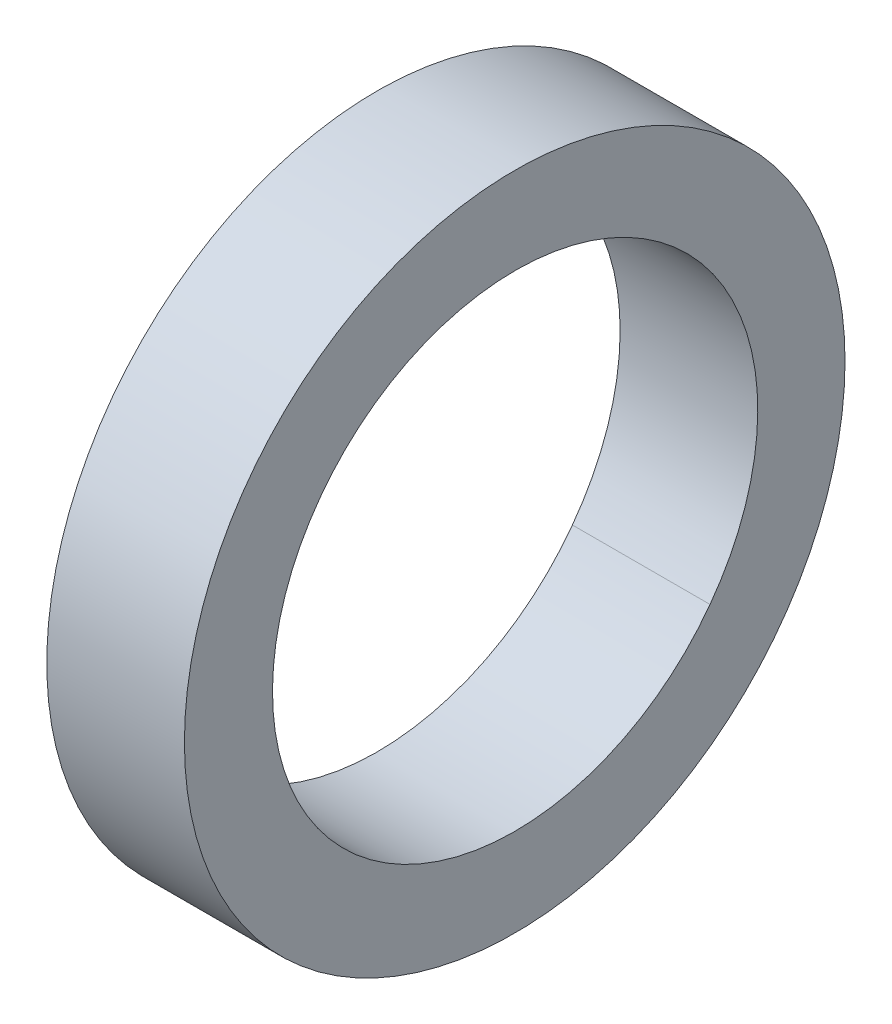
SolidWorks part; units mm, degrees
ref_plane "Front Plane" through (0, 0, 0) normal (0, 0, 1) x (1, 0, 0)
ref_plane "Top Plane" through (0, 0, 0) normal (0, 1, 0) x (1, 0, 0)
ref_plane "Right Plane" through (0, 0, 0) normal (1, 0, 0) x (0, 0, -1)
sketch "Sketch1" plane through (0, 0, 0) normal (0, 1, 0) x (1, 0, 0)
  line L1 (-100, 100) -> (100, 100)
  line L2 (-100, 100) -> (-100, -100)
  line L3 (-100, -100) -> (100, -100)
  line L4 (100, 100) -> (100, -100)
  line L5 (-100, 100) -> (100, -100) construction
  line L6 (-100, -100) -> (100, 100) construction
  point P0 (0, 0)
extrude "Boss-Extrude1" add sketch "Sketch1" along normal blind 30
sketch "Sketch4" plane through (0, 30, 0) normal (0, 1, 0) x (1, 0, 0)
  line L1 (-87.5, -87.5) -> (87.5, -87.5)
  line L2 (-87.5, -87.5) -> (-87.5, 87.5)
  line L3 (-87.5, 87.5) -> (87.5, 87.5)
  line L4 (87.5, -87.5) -> (87.5, 87.5)
  line L5 (-87.5, -87.5) -> (87.5, 87.5) construction
  line L6 (-87.5, 87.5) -> (87.5, -87.5) construction
  point P0 (0, 0)
extrude "Cut-Extrude1" cut sketch "Sketch4" against normal blind 30
sketch "Sketch7" plane through (-100, 0, 0) normal (-1, 0, 0) x (0, 0, 1)
  circle A0 centre (0, 15) radius 4
extrude "Cut-Extrude2" cut sketch "Sketch7" against normal blind 210
sketch "Sketch10" plane through (-100, 0, 0) normal (-1, 0, 0) x (0, 0, 1)
  line L0 (-8.6266, 30) -> (-8.6266, 0)
  line L1 (-100, 30) -> (100, 30) construction
  line L2 (-100, 0) -> (100, 0) construction
  line L3 (-8.6266, 0) -> (-14.6668, 0)
  line L4 (-14.6668, 0) -> (-14.6668, 30)
  line L5 (-14.6668, 30) -> (-8.6266, 30)
extrude "Boss-Extrude2" add sketch "Sketch10" along normal blind 20
sketch "Sketch11" plane through (0, 0, -8.6266) normal (0, 0, 1) x (1, 0, 0)
  line L0 (-120, 0) -> (-120, 30)
  line L1 (-120, 30) -> (-110, 30)
  line L2 (-120, 30) -> (-100, 30) construction
  line L3 (-110, 30) -> (-110, 0)
  line L4 (-120, 0) -> (-100, 0) construction
  line L5 (-110, 0) -> (-120, 0)
extrude "Boss-Extrude3" add sketch "Sketch11" along normal blind 20
sketch "Sketch12" plane through (100, 0, 0) normal (1, 0, 0) x (0, 0, -1)
  circle A0 centre (0, 15) radius 4
extrude "Cut-Extrude3" cut sketch "Sketch12" against normal blind 231
sketch "Sketch13" plane through (0, 30, 0) normal (0, 1, 0) x (1, 0, 0)
  circle A0 centre (-93.6945, -93.0455) radius 4
extrude "Cut-Extrude5" cut sketch "Sketch13" against normal blind 231
sketch "Sketch14" plane through (0, 0, 100) normal (0, 0, 1) x (1, 0, 0)
  circle A0 centre (0, 13.6147) radius 4
extrude "Cut-Extrude6" cut sketch "Sketch14" against normal blind 250.5
sketch "Sketch15" plane through (100, 0, 0) normal (1, 0, 0) x (0, 0, -1)
  circle A0 centre (0, 15) radius 30
  circle A1 centre (0, 15) radius 22
extrude "Boss-Extrude5" add sketch "Sketch15" against normal blind 201
sketch "Sketch17" plane through (100, 0, 0) normal (1, 0, 0) x (0, 0, -1)
  circle A0 centre (0.0744, 15.1008) radius 22
extrude "Cut-Extrude7" cut sketch "Sketch17" against normal blind 201
sketch "Sketch18" plane through (87.5, 0, 0) normal (-1, 0, 0) x (0, 0, 1)
  line L1 (-87.5, 0) -> (87.5, 0)
  line L2 (-87.5, 0) -> (-87.5, 30)
  line L3 (-87.5, 30) -> (87.5, 30)
  line L4 (87.5, 0) -> (87.5, 30)
sketch "Sketch21" plane through (0, 0, -14.6668) normal (0, 0, -1) x (-1, 0, 0)
  line L0 (120, 30) -> (120, 0) construction
  line L1 (120, 1.1441) -> (110.5, 1.1441)
  line L2 (120, 1.1441) -> (120, 30)
  line L3 (120, 30) -> (110.5, 30)
  line L4 (110.5, 1.1441) -> (110.5, 30)
  line L5 (120, 30) -> (101, 30) construction
extrude "Boss-Extrude6" add sketch "Sketch21" along normal blind 26
sketch "Sketch22" plane through (0, 30, 0) normal (0, 1, 0) x (1, 0, 0)
  line L1 (-110.5, 14.6668) -> (-101, 14.6668)
  line L2 (-110.5, 14.6668) -> (-110.5, 8.6266)
  line L3 (-110.5, 8.6266) -> (-101, 8.6266)
  line L4 (-101, 14.6668) -> (-101, 8.6266)
extrude "Cut-Extrude10" cut sketch "Sketch22" against normal blind 49
sketch "Sketch23" plane through (-110.5, 0, 0) normal (1, 0, 0) x (0, 0, -1)
  line L0 (40.6668, 1.1441) -> (14.6668, 1.1441) construction
  line L1 (40.6668, 30) -> (30.6579, 30)
  line L2 (40.6668, 30) -> (40.6668, 1.1441)
  line L3 (40.6668, 1.1441) -> (30.6579, 1.1441)
  line L4 (30.6579, 30) -> (30.6579, 1.1441)
extrude "Boss-Extrude7" add sketch "Sketch23" along normal blind 21
sketch "Sketch24" plane through (0, 0, -14.6668) normal (0, 0, -1) x (-1, 0, 0)
  line L1 (120, 0) -> (110.5, 0)
  line L2 (120, 0) -> (120, 1.1441)
  line L3 (120, 1.1441) -> (110.5, 1.1441)
  line L4 (110.5, 0) -> (110.5, 1.1441)
extrude "Cut-Extrude11" cut sketch "Sketch24" against normal blind 27
sketch "Sketch26" plane through (0, 0, 0) normal (0, -1, 0) x (1, 0, 0)
  line L1 (-110.5, -8.6266) -> (-109.9986, -8.6266)
  line L2 (-110.5, -8.6266) -> (-110.5, 12.267)
  line L3 (-110.5, 12.267) -> (-109.9986, 12.267)
  line L4 (-109.9986, -8.6266) -> (-109.9986, 12.267)
extrude "Cut-Extrude12" cut sketch "Sketch26" against normal blind 35
sketch "Sketch27" plane through (-87.5, 0, 0) normal (1, 0, 0) x (0, 0, -1)
  circle A0 centre (-31.9164, 15.3761) radius 49.1928
extrude "Cut-Extrude13" cut sketch "Sketch27" along normal blind 175
sketch "Sketch28" plane through (-87.5, 0, 0) normal (1, 0, 0) x (0, 0, -1)
  circle A0 centre (37.7624, 15.4944) radius 41.209
extrude "Cut-Extrude14" cut sketch "Sketch28" along normal blind 175
sketch "Sketch29" plane through (100, 0, 0) normal (1, 0, 0) x (0, 0, -1)
  circle A0 centre (0, 15) radius 30
sketch "Sketch31" plane through (100, 0, 0) normal (1, 0, 0) x (0, 0, -1)
  arc A0 (25.9808, 30) -> (25.2968, 31.1267) centre (0, 15) cw
extrude "Cut-Extrude15" cut sketch "Sketch31" against normal blind 220 and the other way through all body kept at (-101, 15, -30) body kept at (-110.5, 1.1441, 11.3734)
sketch "Sketch33" plane through (100, 0, 0) normal (1, 0, 0) x (0, 0, -1)
  circle A0 centre (0, 15) radius 22
extrude "Cut-Extrude16" cut sketch "Sketch33" against normal blind 220
sketch "Sketch34" plane through (-120, 0, 0) normal (-1, 0, 0) x (0, 0, 1)
  line L1 (-16.0935, 30) -> (-31.9803, 30)
  line L2 (-16.0935, 30) -> (-16.0935, -9.2595)
  line L3 (-16.0935, -9.2595) -> (-31.9803, -9.2595)
  line L4 (-31.9803, 30) -> (-31.9803, -9.2595)
extrude "Cut-Extrude17" cut sketch "Sketch34" against normal blind 14
sketch "Sketch35" plane through (87.5, 0, 0) normal (-1, 0, 0) x (0, 0, 1)
  circle A0 centre (-0.8608, 19.9092) radius 61.8102
extrude "Cut-Extrude18" cut sketch "Sketch35" along normal blind 218
